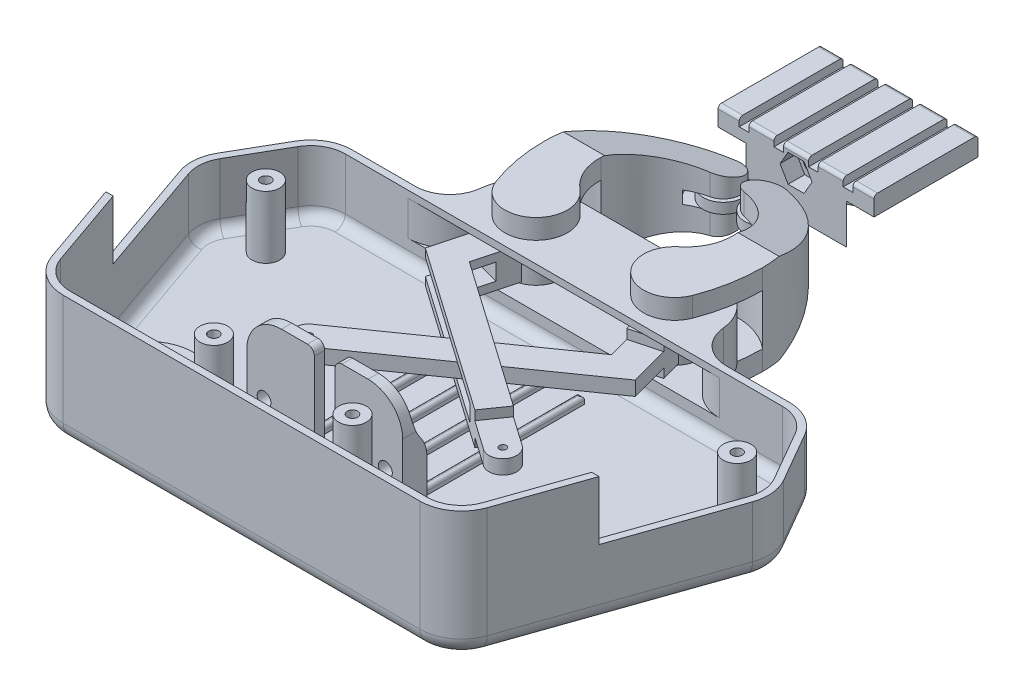
SolidWorks part; units mm, degrees
ref_plane "Front Plane" through (0, 0, 0) normal (0, 0, 1) x (1, 0, 0)
ref_plane "Top Plane" through (0, 0, 0) normal (0, 1, 0) x (1, 0, 0)
ref_plane "Right Plane" through (0, 0, 0) normal (1, 0, 0) x (0, 0, -1)
sketch "Sketch1" plane through (0, 0, 0) normal (0, 1, 0) x (1, 0, 0)
  line L0 (-70, -55) -> (-35, -55)
  line L1 (70, -55) -> (84.4338, -80)
  line L2 (84.4338, -80) -> (60, -150)
  line L3 (60, -150) -> (-60, -150)
  line L4 (-60, -150) -> (-84.4338, -80)
  line L5 (-84.4338, -80) -> (-70, -55)
  line L6 (-35, -55) -> (-35, -35)
  line L7 (-35, -35) -> (35, -35)
  line L8 (35, -35) -> (35, -55)
  line L9 (0, -55) -> (0, -122.8119) construction
  line L10 (35, -55) -> (70, -55)
  point P15 (0, -150)
  dimension "D1" = 25
  dimension "D2" = 140
  dimension "D3" = 70
  dimension "D4" = 120
  dimension "D5" = 70
  dimension "D6" = 55
  dimension "D7" = 120
  dimension "D8" = 20
  dimension "D9" = 70
  dimension "D10" = 35
extrude "Boss-Extrude1" add sketch "Sketch1" along normal blind 2
sketch "Sketch2" plane through (0, 2, 0) normal (0, 1, 0) x (1, 0, 0)
  line L0 (84.4338, -80) -> (70, -55) construction
  line L1 (60, -150) -> (84.4338, -80) construction
  line L2 (-60, -150) -> (60, -150) construction
  line L3 (-84.4338, -80) -> (-60, -150) construction
  line L4 (-70, -55) -> (-84.4338, -80) construction
  line L6 (84.4338, -80) -> (70, -55)
  line L7 (60, -150) -> (84.4338, -80)
  line L8 (-60, -150) -> (60, -150)
  line L9 (-84.4338, -80) -> (-60, -150)
  line L10 (-70, -55) -> (-84.4338, -80)
  line L11 (70, -55) -> (35, -55)
  line L12 (68.8453, -57) -> (33, -57)
  line L13 (-68.8453, -57) -> (-82.2434, -80.2062)
  line L14 (-82.2434, -80.2062) -> (-58.5798, -148)
  line L15 (-58.5798, -148) -> (58.5798, -148)
  line L16 (58.5798, -148) -> (82.2434, -80.2062)
  line L17 (82.2434, -80.2062) -> (68.8453, -57)
  line L18 (-35, -55) -> (-35, -35)
  line L19 (-35, -35) -> (35, -35)
  line L20 (35, -35) -> (35, -55)
  line L21 (-35, -55) -> (-70, -55)
  line L22 (-33, -57) -> (-33, -37)
  line L23 (70, -55) -> (-70, -55) construction
  line L24 (-33, -37) -> (33, -37)
  line L25 (33, -37) -> (33, -57)
  line L26 (-33, -57) -> (-68.8453, -57)
  line L28 (68.8453, -57) -> (-68.8453, -57) construction
  dimension "D1" = 2
  dimension "D2" = 2
  dimension "D3" = 2
  dimension "D4" = 2
extrude "Boss-Extrude2" add sketch "Sketch2" along normal blind 35
sketch "Sketch20" plane through (0, 0, 0) normal (0, -1, 0) x (1, 0, 0)
  line L0 (70, 55) -> (35, 55) construction
  line L1 (-35, 35) -> (35, 35)
  line L2 (-35, 35) -> (-35, 55)
  line L3 (-35, 55) -> (35, 55)
  line L4 (35, 35) -> (35, 55)
  line L5 (35, 55) -> (35, 35) construction
  line L6 (35, 35) -> (-35, 35) construction
  line L7 (-35, 35) -> (-35, 55) construction
extrude "Cut-Extrude7" cut sketch "Sketch20" against normal blind 8
sketch "Sketch21" plane through (0, 8, 0) normal (0, -1, 0) x (1, 0, 0)
  line L1 (-35, 35) -> (35, 35)
  line L2 (-35, 35) -> (-35, 55)
  line L3 (-35, 55) -> (35, 55)
  line L4 (35, 35) -> (35, 55)
extrude "Boss-Extrude12" add sketch "Sketch21" along normal blind 2
sketch "Sketch22" plane through (0, 0, 55) normal (0, 0, 1) x (1, 0, 0)
  line L1 (-33, 2) -> (33, 2)
  line L2 (-33, 2) -> (-33, 8)
  line L3 (-33, 8) -> (33, 8)
  line L4 (33, 2) -> (33, 8)
extrude "Boss-Extrude13" add sketch "Sketch22" along normal blind 2
sketch "Sketch23" plane through (0, 37, 0) normal (0, 1, 0) x (1, 0, 0)
  line L0 (35, -35) -> (-35, -35) construction
  line L1 (-35, -57) -> (35, -57)
  line L2 (-35, -57) -> (-35, -35)
  line L3 (-35, -35) -> (35, -35)
  line L4 (35, -57) -> (35, -35)
  line L5 (-35, -35) -> (-35, -55) construction
  line L6 (35, -55) -> (35, -35) construction
  line L7 (33, -57) -> (-33, -57) construction
extrude "Cut-Extrude8" cut sketch "Sketch23" against normal offset from surface (19 mm away) 12 up to face at (0, 6, 45)
sketch "Sketch24" plane through (0, 18, 0) normal (0, 1, 0) x (1, 0, 0)
  line L1 (-35, -35) -> (35, -35)
  line L2 (-35, -35) -> (-35, -57)
  line L3 (-35, -57) -> (35, -57)
  line L4 (35, -35) -> (35, -57)
  line L5 (-35, -35) -> (35, -35) construction
  line L6 (-35, -55) -> (-35, -35) construction
  line L8 (35, -35) -> (35, -55) construction
  line L9 (-35, -57) -> (-68.8453, -57) construction
extrude "Boss-Extrude16" add sketch "Sketch24" along normal blind 2
sketch "Sketch26" plane through (0, 0, 0) normal (0, -1, 0) x (1, 0, 0)
  line L0 (0, 35) -> (0, 168.1743) construction
  line L1 (-35, 35) -> (35, 35) construction
  circle A0 centre (20, 45) radius 7.5
  circle A1 centre (-20, 45) radius 7.5
  dimension "D1" = 15
  dimension "D2" = 10
  dimension "D3" = 20
extrude "Cut-Extrude9" cut sketch "Sketch26" against normal through all
sketch "Sketch27" plane through (0, 8, 0) normal (0, 1, 0) x (1, 0, 0)
  line L0 (-29.5, -45) -> (-27.5, -45)
  line L1 (-10.5, -45) -> (-12.5, -45)
  line L2 (0, -35) -> (0, -72.4721) construction
  line L3 (35, -35) -> (-35, -35) construction
  line L4 (29.5, -45) -> (27.5, -45)
  line L5 (10.5, -45) -> (12.5, -45)
  arc A0 (-27.5, -45) -> (-12.5, -45) centre (-20, -45) cw
  circle A1 centre (-20, -45) radius 7.5 construction
  arc A2 (-10.5, -45) -> (-29.5, -45) centre (-20, -45) ccw
  arc A3 (27.5, -45) -> (12.5, -45) centre (20, -45) ccw
  arc A4 (10.5, -45) -> (29.5, -45) centre (20, -45) cw
  dimension "D1" = 9.5
extrude "Boss-Extrude18" add sketch "Sketch27" along normal up to surface (10 mm away) up to face at (20, 18, 52.5)
sketch "Sketch25" plane through (0, 20, 0) normal (0, 1, 0) x (1, 0, 0)
  line L0 (35, -57) -> (35, -55) construction
  line L1 (-35, -57) -> (35, -57)
  line L2 (-35, -57) -> (-35, -55)
  line L3 (-35, -55) -> (35, -55)
  line L4 (35, -57) -> (35, -55)
  line L5 (-35, -57) -> (35, -57) construction
  line L6 (-35, -55) -> (-35, -57) construction
  line L7 (-35, -55) -> (-70, -55) construction
extrude "Boss-Extrude17" add sketch "Sketch25" along normal up to surface (17 mm away) up to face at (0, 37, 85.2758)
fillet "Fillet8" radius 10 2 edges at (-33, 13, 37) (33, 13, 37)
fillet "Fillet9" radius 12 2 edges at (35, 13, 35) (-35, 13, 35)
sketch "Sketch32" plane through (0, 6, 0) normal (0, -1, 0) x (1, 0, 0)
  circle A0 centre (-20, 45) radius 7.35
  circle A1 centre (-20, 45) radius 7.5 construction
  dimension "D1" = 14.7
extrude "Boss-Extrude22" add sketch "Sketch32" against normal offset from surface (14.6 mm away) 0.3 from offset 0.3 separate body up to face at (0, 20, 44.8382) offset beyond the face yes
ref_plane "Plane6" through (0, 13, 0) normal (0, -1, 0) x (-1, 0, 0)
sketch "Sketch34" plane through (0, 13, 0) normal (0, -1, 0) x (-1, 0, 0)
  line L0 (0, -55) -> (0, -6.1056) construction
  line L1 (-35, -55) -> (35, -55) construction
  circle A0 centre (6, -5) radius 6
  circle A1 centre (20, -45) radius 7.5 construction
  circle A2 centre (20, -45) radius 7.5 construction
  circle A3 centre (6, -5) radius 2.8
  dimension "D1" = 12
  dimension "D3" = 5.6
  dimension "D2" = 40
extrude "Boss-Extrude23" add sketch "Sketch34" along normal mid plane 3 separate body
sketch "Sketch36" plane through (0, 13, 0) normal (0, -1, 0) x (-1, 0, 0)
  circle A0 centre (6, -5) radius 2.5
  dimension "D1" = 5
extrude "Boss-Extrude24" add sketch "Sketch36" along normal mid plane 3.6 separate body
sketch "Sketch37" plane through (0, 11.2, 0) normal (0, -1, 0) x (1, 0, 0)
  line L0 (-1.0405, 27.7489) -> (-20, 45) construction
  line L1 (-6, 5) -> (-1.0405, 27.7489) construction
  line L2 (0.4875, 31.2396) -> (-20, 45) construction
  line L3 (0.4875, 31.2396) -> (-6, 5) construction
  arc A0 (-4.935, 9.8853) -> (-7.2001, 0.1462) centre (-6, 5) cw
  circle A1 centre (-20, 45) radius 7.35 construction
  arc A2 (-14.5636, 40.0535) -> (-26.1015, 49.0981) centre (-20, 45) ccw construction
  arc A3 (-4.935, 9.8853) -> (-14.5636, 40.0535) centre (-1.0405, 27.7489) cw construction
  arc A4 (-26.1015, 49.0981) -> (-7.2001, 0.1462) centre (0.4875, 31.2396) ccw construction
  arc A5 (-31.5421, 31.1877) -> (-19.3089, 27.0133) centre (-20, 45) ccw
  arc A6 (-31.5421, 31.1877) -> (-7.2001, 0.1462) centre (0.4875, 31.2396) ccw
  arc A7 (-19.3089, 27.0133) -> (-4.935, 9.8853) centre (-1.0405, 27.7489) ccw
  dimension "D1" = 5
  dimension "D4" = 18
  dimension "D2" = 60
  dimension "D3" = 70
extrude "Boss-Extrude25" add sketch "Sketch37" along normal up to surface (11.2 mm away) up to face at (0, 0, 95)
sketch "Sketch39" plane through (0, 5.7, 0) normal (0, -1, 0) x (1, 0, 0)
  arc A0 (-14.3353, 38.0064) -> (-28.4038, 48.2211) centre (-20, 45) ccw
  arc A1 (-31.5421, 31.1877) -> (-19.3089, 27.0133) centre (-20, 45) ccw construction
  arc A2 (-31.5421, 31.1877) -> (-19.3089, 27.0133) centre (-20, 45) ccw
  arc A3 (-31.5421, 31.1877) -> (-28.4038, 48.2211) centre (15.8356, 31.2644) cw
  arc A4 (-31.5421, 31.1877) -> (-7.2001, 0.1462) centre (0.4875, 31.2396) ccw construction
  arc A5 (-19.3089, 27.0133) -> (-14.3353, 38.0064) centre (-5.8694, 27.5545) cw
  arc A6 (-19.3089, 27.0133) -> (-4.935, 9.8853) centre (-1.0405, 27.7489) ccw construction
  dimension "D1" = 18
extrude "Boss-Extrude26" add sketch "Sketch39" along direction (0, -1, 0) on the side of the normal up to surface (5.7 mm away) up to face at (-16.6764, 0, 14.8256)
sketch "Sketch40" plane through (0, 20.3, 0) normal (0, 1, 0) x (1, 0, 0)
  arc A1 (-28.4038, -48.2211) -> (-14.3353, -38.0064) centre (-20, -45) ccw construction
  arc A2 (-19.3089, -27.0133) -> (-14.3353, -38.0064) centre (-5.8694, -27.5545) ccw construction
  arc A3 (-19.3089, -27.0133) -> (-31.5421, -31.1877) centre (-20, -45) ccw construction
  arc A4 (-31.5421, -31.1877) -> (-28.4038, -48.2211) centre (15.8356, -31.2644) ccw construction
  arc A5 (-28.4038, -48.2211) -> (-14.3353, -38.0064) centre (-20, -45) ccw
  arc A6 (-19.3089, -27.0133) -> (-14.3353, -38.0064) centre (-5.8694, -27.5545) ccw
  arc A7 (-19.3089, -27.0133) -> (-31.5421, -31.1877) centre (-20, -45) ccw
  arc A8 (-31.5421, -31.1877) -> (-28.4038, -48.2211) centre (15.8356, -31.2644) ccw
extrude "Boss-Extrude27" add sketch "Sketch40" along normal blind 5.7
sketch "Sketch41" plane through (0, 14.8, 0) normal (0, 1, 0) x (1, 0, 0)
  arc A0 (-4.935, -9.8853) -> (-7.2001, -0.1462) centre (-6, -5) ccw construction
  arc A1 (-19.3089, -27.0133) -> (-31.5421, -31.1877) centre (-20, -45) ccw construction
  arc A2 (-4.935, -9.8853) -> (-19.3089, -27.0133) centre (-1.0405, -27.7489) ccw construction
  arc A3 (-7.2001, -0.1462) -> (-31.5421, -31.1877) centre (0.4875, -31.2396) ccw construction
  arc A4 (-4.935, -9.8853) -> (-7.2001, -0.1462) centre (-6, -5) ccw
  arc A5 (-19.3089, -27.0133) -> (-31.5421, -31.1877) centre (-20, -45) ccw
  arc A6 (-4.935, -9.8853) -> (-19.3089, -27.0133) centre (-1.0405, -27.7489) ccw
  arc A7 (-7.2001, -0.1462) -> (-31.5421, -31.1877) centre (0.4875, -31.2396) ccw
extrude "Boss-Extrude28" add sketch "Sketch41" along normal up to surface (11.2 mm away) up to face at (-22.3518, 26, 38.2988)
sketch "Sketch43" plane through (0, 11.2, 0) normal (0, 1, 0) x (1, 0, 0)
  arc A1 (-4.935, -9.8853) -> (-19.3089, -27.0133) centre (-1.0405, -27.7489) ccw construction
  arc A3 (-19.3089, -27.0133) -> (-31.5421, -31.1877) centre (-20, -45) ccw construction
  arc A5 (-10.5871, -12.156) -> (-19.3089, -27.0133) centre (-1.0405, -27.7489) ccw
  arc A6 (-7.2001, -0.1462) -> (-31.5421, -31.1877) centre (0.4875, -31.2396) ccw construction
  arc A7 (-19.3089, -27.0133) -> (-31.5421, -31.1877) centre (-20, -45) ccw
  arc A8 (-14.2045, -2.7783) -> (-10.5871, -12.156) centre (-6, -5) ccw
  arc A9 (-14.2045, -2.7783) -> (-31.5421, -31.1877) centre (0.4875, -31.2396) ccw
  arc A13 (-4.935, -9.8853) -> (-7.2001, -0.1462) centre (-6, -5) ccw construction
  dimension "D1" = 17
extrude "Boss-Extrude29" add sketch "Sketch43" along normal up to surface (3.6 mm away) up to face at (-6, 14.8, 2.5)
sketch "Sketch44" plane through (0, 0, 0) normal (1, 0, 0) x (0, 0, -1)
  line L0 (0, 17.8) -> (-26.0133, 26)
  line L1 (-26.0133, 26) -> (0, 26)
  line L4 (0, 14.8) -> (0, 26) construction
  line L5 (-9.8853, 26) -> (-27.0133, 26) construction
  line L6 (0, 17.8) -> (0, 26)
  line L7 (-15.422, 13) -> (22.0298, 13) construction
  line L8 (-94.4278, 13) -> (94.4278, 13) construction
  line L9 (0, 8.2) -> (-26.0133, 0)
  line L10 (-26.0133, 0) -> (0, 0)
  line L11 (0, 8.2) -> (0, 0)
  dimension "D1" = 1
  dimension "D2" = 3
extrude "Cut-Extrude10" cut sketch "Sketch44" against normal up to surface (31.1129 mm away) up to face at (-19.4224, 13, 12.2098)
ref_plane "Plane2" through (0, 0, 0) normal (1, 0, 0) x (0, 0, -1)
ref_plane "Plane3" through (0, 0, 126) normal (0, 0, -1) x (-1, 0, 0)
sketch "Sketch45" plane through (0, 13, 0) normal (0, -1, 0) x (-1, 0, 0)
  circle A0 centre (6, -5) radius 6 construction
  circle A1 centre (6, -5) radius 6
  circle A2 centre (6, -5) radius 5.75
  dimension "D1" = 11.5
extrude "Cut-Extrude11" cut sketch "Sketch45" along normal up to surface (1.5 mm away) from surface up to face at (-6, 11.5, -1) starting at face at (-6, 14.5, -1)
mirror "Mirror8" about plane through (0, 0, 0) normal (1, 0, 0) of bodies 137 140
sketch "Sketch8" plane through (0, 0, 126) normal (0, 0, -1) x (-1, 0, 0)
  line L0 (-68.8453, 2) -> (68.8453, 2) construction
  line L1 (-68.8453, 2) -> (68.8453, 2) construction
  line L2 (60, 0) -> (-60, 0) construction
  line L3 (22.5, 2) -> (-22.5, 2)
  line L4 (22.5, 2) -> (22.5, 36)
  line L5 (22.5, 36) -> (-22.5, 36)
  line L6 (-22.5, 2) -> (-22.5, 36)
  line L7 (60, 0) -> (-60, 0) construction
  line L8 (0, 14.8493) -> (0, -14.8493) construction
  dimension "D1" = 34
  dimension "D2" = 45
  dimension "D3" = 22.5
extrude "Boss-Extrude5" add sketch "Sketch8" along normal blind 3
sketch "Sketch9" plane through (0, 2, 0) normal (0, 1, 0) x (1, 0, 0)
  line L1 (-22.5, -123) -> (-19.5, -123)
  line L2 (-22.5, -123) -> (-22.5, -119)
  line L3 (-22.5, -119) -> (-19.5, -119)
  line L4 (-19.5, -123) -> (-19.5, -119)
  line L5 (22.5, -123) -> (19.5, -123)
  line L6 (22.5, -123) -> (22.5, -119)
  line L7 (22.5, -119) -> (19.5, -119)
  line L8 (19.5, -123) -> (19.5, -119)
  dimension "D1" = 3
  dimension "D2" = 4
extrude "Boss-Extrude6" add sketch "Sketch9" along normal blind 20
fillet "Fillet1" radius 10 2 edges at (-21, 22, 123) (21, 22, 123)
fillet "Fillet2" radius 10 2 edges at (-21, 22, 119) (21, 22, 119)
sketch "Sketch11" plane through (0, 2, 0) normal (0, 1, 0) x (1, 0, 0)
  line L0 (-58.5798, -148) -> (58.5798, -148) construction
  circle A0 centre (-43.5798, -133) radius 12.5
  dimension "D1" = 25
  dimension "D2" = 15
  dimension "D3" = 15
extrude "Boss-Extrude9" add sketch "Sketch11" along normal blind 10
ref_plane "Plane4" through (0, 7, 0) normal (0, 1, 0) x (1, 0, 0)
sketch "Sketch13" plane through (0, 7, 0) normal (0, 1, 0) x (1, 0, 0)
  line L0 (-53.0211, -136.2955) -> (-58.294, -121.1894)
  line L1 (-82.2434, -80.2062) -> (-58.5798, -148) construction
  line L2 (-34.1384, -129.7045) -> (-39.4113, -114.5983)
  line L3 (-58.294, -121.1894) -> (-39.4113, -114.5983)
  arc A0 (-53.0211, -136.2955) -> (-34.1384, -129.7045) centre (-43.5798, -133) ccw
  dimension "D1" = 20
  dimension "D2" = 16
extrude "Cut-Extrude3" cut sketch "Sketch13" along normal blind 5 from offset 3 offset against normal yes
sketch "Sketch14" plane through (0, 12, 0) normal (0, 1, 0) x (1, 0, 0)
  circle A0 centre (-43.5798, -133) radius 2.5
  circle A1 centre (-43.5798, -133) radius 12.5 construction
  dimension "D1" = 5
extrude "Cut-Extrude4" cut sketch "Sketch14" against normal up to surface (8 mm away) up to face at (-44.4037, 4, 130.6397)
sketch "Sketch15" plane through (0, 0, 126) normal (0, 0, 1) x (1, 0, 0)
  line L1 (22.5, 2) -> (-22.5, 2) construction
  line L2 (22.5, 2) -> (-22.5, 2) construction
  line L3 (0, -14.8493) -> (0, 14.8493) construction
  circle A0 centre (17.5, 16) radius 2
  circle A1 centre (-17.5, 16) radius 2
  circle A3 centre (0, 8) radius 4.65
  dimension "D1" = 8
  dimension "D2" = 4
  dimension "D3" = 4
  dimension "D6" = 9.3
  dimension "D4" = 35
  dimension "D5" = 17.5
  dimension "D7" = 6
extrude "Cut-Extrude5" cut sketch "Sketch15" against normal up to surface (3 mm away) up to face at (0, 24.5, 123)
fillet "Fillet3" radius 10 8 edges at (-35, 13, 55) (35, 13, 55) (58.5798, 19.5, 148) (-58.5798, 19.5, 148) (82.2434, 19.5, 80.2062) (68.8453, 19.5, 57) (-82.2434, 19.5, 80.2062) (-68.8453, 19.5, 57)
fillet "Fillet4" radius 12 8 edges at (-60, 18.5, 150) (-84.4338, 18.5, 80) (-70, 18.5, 55) (-33, 13, 57) (33, 13, 57) (70, 18.5, 55) (60, 18.5, 150) (84.4338, 18.5, 80)
fillet "Fillet5" radius 10 2 edges at (22.5, 36, 124.5) (-22.5, 36, 124.5)
fillet "Fillet6" radius 3 12 edges at (-70.8266, 2, 112.9143) (-81.2478, 2, 80.3) (-75.842, 2, 69.1187) (-68.0718, 2, 58.3397) (0, 2, 57) (68.0718, 2, 58.3397) (75.842, 2, 69.1187) (81.2478, 2, 80.3) (70.8266, 2, 112.9143) (0, 2, 148) (-57.2685, 2, 146.1534) (57.2685, 2, 146.1534)
fillet "Fillet7" radius 5 12 edges at (69.0718, 0, 56.6077) (77.5741, 0, 68.1187) (83.2389, 0, 80.1125) (72.7148, 0, 113.5734) (58.4264, 0, 147.7841) (0, 0, 150) (-58.4264, 0, 147.7841) (-72.7148, 0, 113.5734) (-83.2389, 0, 80.1125) (-77.5741, 0, 68.1187) (-69.0718, 0, 56.6077) (0, 0, 55)
sketch "Sketch16" plane through (0, 0, 0) normal (1, 0, 0) x (0, 0, -1)
  line L0 (-83.5443, 0) -> (-140.3069, 0) construction
  line L1 (-118, 40) -> (-28, 40)
  line L2 (-118, 40) -> (-118, 20)
  line L3 (-118, 20) -> (-28, 20)
  line L4 (-28, 40) -> (-28, 20)
  line L5 (-150, 5) -> (-150, 37) construction
  dimension "D1" = 20
  dimension "D2" = 32
  dimension "D3" = 20
  dimension "D4" = 90
extrude "Cut-Extrude6" cut sketch "Sketch16" against normal through all both and the other way through all
sketch "Sketch17" plane through (0, 2, 0) normal (0, 1, 0) x (1, 0, 0)
  line L0 (0, -14.8493) -> (0, 14.8493) construction
  line L4 (-63.0718, -55) -> (-44.9089, -55) construction
  circle A2 centre (-68, -75) radius 4
  circle A4 centre (-68, -75) radius 1.5
  circle A10 centre (68, -75) radius 1.5
  circle A11 centre (68, -75) radius 4
  dimension "D7" = 8
  dimension "D9" = 3
  dimension "D4" = 20
  dimension "D5" = 68
extrude "Boss-Extrude10" add sketch "Sketch17" along normal up to surface (18 mm away) up to face at (0, 20, 71.1525)
sketch "Sketch19" plane through (0, 2, 0) normal (0, 1, 0) x (1, 0, 0)
  line L0 (0, -14.8493) -> (0, 14.8493) construction
  line L1 (-51.4786, -150) -> (51.4786, -150) construction
  circle A0 centre (-20, -138) radius 4
  circle A1 centre (-20, -138) radius 1.5
  circle A2 centre (20, -138) radius 1.5
  circle A3 centre (20, -138) radius 4
  dimension "D1" = 3
  dimension "D2" = 8
  dimension "D3" = 20
  dimension "D4" = 12
extrude "Boss-Extrude11" add sketch "Sketch19" along normal up to surface (35 mm away) up to face at (0, 37, 136.7604)
sketch "Sketch46" plane through (0, 0, 126) normal (0, 0, 1) x (1, 0, 0)
  line L0 (-3, 8) -> (-3, 36)
  line L1 (-3, 36) -> (3, 36)
  line L3 (-3, 8) -> (3, 8)
  line L5 (-12.5, 36) -> (12.5, 36) construction
  line L7 (3, 36) -> (3, 8)
  circle A0 centre (0, 8) radius 4.65 construction
  circle A1 centre (0, 8) radius 4.65 construction
  dimension "D1" = 6
extrude "Cut-Extrude12" cut sketch "Sketch46" against normal up to surface (3 mm away) up to face at (-4.65, 8, 123)
fillet "Fillet10" radius 2 2 edges at (-3, 36, 124.5) (3, 36, 124.5)
mirror "Mirror9" about plane through (0, 0, 0) normal (1, 0, 0) of "Cut-Extrude4", "Cut-Extrude3", "Boss-Extrude9"
sketch "Sketch49" plane through (0, 13, 0) normal (0, -1, 0) x (-1, 0, 0)
  line L0 (20, -45) -> (6, -5) construction
  line L1 (27.0996, -43.0977) -> (32.923, -64.831) construction
  line L2 (30.3078, -66.6622) -> (-25.7197, -105.8931)
  line L3 (12.9004, -46.9023) -> (17.9052, -65.5804) construction
  line L4 (17.9052, -65.5804) -> (-30.3083, -99.3398)
  line L5 (63.0718, -57) -> (-63.0718, -57) construction
  line L6 (30.3078, -66.6622) -> (25.7352, -49.5968)
  line L7 (20.5204, -63.7492) -> (17.3316, -51.8485)
  line L8 (17.9052, -65.5804) -> (20.5204, -63.7492)
  line L9 (30.3078, -66.6622) -> (32.923, -64.831) construction
  circle A0 centre (20, -45) radius 7.35 construction
  arc A1 (17.3316, -51.8485) -> (25.7352, -49.5968) centre (20, -45) ccw
  circle A2 centre (20, -45) radius 75 construction
  arc A3 (7.2001, -0.1462) -> (4.935, -9.8853) centre (6, -5) ccw construction
  arc A4 (7.2001, -0.1462) -> (4.935, -9.8853) centre (6, -5) ccw construction
  arc A5 (-30.3083, -99.3398) -> (-25.7197, -105.8931) centre (-28.014, -102.6165) ccw
  point P15 (26.4546, -40.6906)
  point P19 (0, 0)
  point P20 (27.0996, -43.0977)
  dimension "D1" = 150
  dimension "D2" = 110
  dimension "D3" = 4
  dimension "D4" = 22.5
  dimension "D5" = 35
  dimension "D6" = 3
  dimension "D7" = 3
extrude "Boss-Extrude30" add sketch "Sketch49" along normal offset from surface 0.3 and the other way offset from surface 0.3 separate body up to face at (0, 8, 45.5486) other way up to face at (0, 18, 45.5486)
sketch "Sketch50" plane through (-41.2919, 0, 58.971) normal (-0.5736, 0, 0.8192) x (0.8192, 0, 0.5736)
  line L0 (13.4091, 8.3) -> (13.4091, 17.7) construction
  line L1 (13.4091, 15.4) -> (65.8061, 15.4)
  line L2 (13.4091, 15.4) -> (13.4091, 10.6)
  line L3 (13.4091, 10.6) -> (65.8061, 10.6)
  line L4 (65.8061, 15.4) -> (65.8061, 10.6)
  line L5 (85.8061, 8.3) -> (85.8061, 17.7) construction
  line L6 (13.4091, 15.4) -> (13.4091, 17.7) construction
  line L7 (81.8061, 17.7) -> (13.4091, 17.7) construction
  line L8 (13.4091, 10.6) -> (13.4091, 8.3) construction
  line L9 (13.4091, 8.3) -> (81.8061, 8.3) construction
  dimension "D1" = 4.8
  dimension "D2" = 0
  dimension "D3" = 20
extrude "Cut-Extrude13" cut sketch "Sketch50" against normal up to surface (8 mm away) up to face at (4.894, 13, 81.5445)
sketch "Sketch51" plane through (0, 13, 0) normal (0, -1, 0) x (-1, 0, 0)
  line L0 (30.3078, -66.6622) -> (25.7352, -49.5968) construction
  line L1 (17.3316, -51.8485) -> (20.5204, -63.7492) construction
  line L3 (-25.7197, -105.8931) -> (30.3078, -66.6622) construction
  line L6 (20.5204, -63.7492) -> (-30.3083, -99.3398) construction
  line L22 (17.3316, -51.8485) -> (20.5204, -63.7492) construction
  line L23 (20.5204, -63.7492) -> (-30.3083, -99.3398) construction
  line L24 (-25.7197, -105.8931) -> (30.3078, -66.6622) construction
  line L25 (30.3078, -66.6622) -> (25.7352, -49.5968) construction
  line L26 (0, 14.8493) -> (0, -14.8493) construction
  line L27 (-20.5204, -63.7492) -> (30.3083, -99.3398)
  line L28 (-17.3316, -51.8485) -> (-20.5204, -63.7492)
  line L29 (-30.3078, -66.6622) -> (-25.7352, -49.5968)
  line L30 (25.7197, -105.8931) -> (-30.3078, -66.6622)
  arc A0 (17.3316, -51.8485) -> (25.7352, -49.5968) centre (20, -45) ccw construction
  arc A6 (-30.3083, -99.3398) -> (-25.7197, -105.8931) centre (-28.014, -102.6165) ccw construction
  arc A10 (-30.3083, -99.3398) -> (-25.7197, -105.8931) centre (-28.014, -102.6165) ccw construction
  arc A11 (17.3316, -51.8485) -> (25.7352, -49.5968) centre (20, -45) ccw construction
  arc A12 (30.3083, -99.3398) -> (25.7197, -105.8931) centre (28.014, -102.6165) cw
  arc A13 (-17.3316, -51.8485) -> (-25.7352, -49.5968) centre (-20, -45) cw
extrude "Boss-Extrude32" add sketch "Sketch51" along normal offset from surface 0.3 and the other way offset from surface 0.4 up to face at (-9.3465, 10.6, 75.4798) other way up to face at (-9.3465, 15.4, 75.4798)
sketch "Sketch52" plane through (0, 13, 0) normal (0, -1, 0) x (-1, 0, 0)
  line L2 (-25.7352, -49.5968) -> (-30.3078, -66.6622) construction
  line L3 (-20.5204, -63.7492) -> (-17.3316, -51.8485) construction
  line L6 (-25.7352, -49.5968) -> (-27.3076, -55.4652)
  line L7 (-18.9041, -57.717) -> (-17.3316, -51.8485)
  line L9 (-18.9041, -57.717) -> (-27.3076, -55.4652)
  line L10 (63.0718, -57) -> (-63.0718, -57) construction
  arc A0 (-25.7352, -49.5968) -> (-17.3316, -51.8485) centre (-20, -45) ccw construction
  arc A1 (-25.7352, -49.5968) -> (-17.3316, -51.8485) centre (-20, -45) ccw
  circle A2 centre (-20, -45) radius 12 construction
  point P2 (-27.4936, -56.1593)
extrude "Boss-Extrude33" add sketch "Sketch52" along normal up to surface (4.7 mm away) from surface up to face at (-5.8265, 8.3, 73.4601) starting at face at (-5.8265, 17.7, 73.4601)
sketch "Sketch53" plane through (0, 17.7, 0) normal (0, 1, 0) x (1, 0, 0)
  line L0 (-20.5204, -63.7492) -> (30.3083, -99.3398) construction
  line L1 (25.7197, -105.8931) -> (-30.3078, -66.6622) construction
  line L2 (21.8792, -93.4377) -> (30.3083, -99.3398)
  line L3 (25.7197, -105.8931) -> (17.2906, -99.9909)
  line L4 (17.2906, -99.9909) -> (21.8792, -93.4377)
  arc A0 (25.7197, -105.8931) -> (30.3083, -99.3398) centre (28.014, -102.6165) ccw construction
  arc A1 (25.7197, -105.8931) -> (30.3083, -99.3398) centre (28.014, -102.6165) ccw
  point P5 (31.2906, -104.9108)
  dimension "D1" = 14
extrude "Cut-Extrude14" cut sketch "Sketch53" against normal up to surface (2.7 mm away) up to face at (6.2892, 15, 75.1868)
sketch "Sketch54" plane through (0, 8.3, 0) normal (0, -1, 0) x (1, 0, 0)
  line L0 (25.7197, 105.8931) -> (17.2906, 99.9909) construction
  line L1 (21.8792, 93.4377) -> (30.3083, 99.3398) construction
  line L2 (17.2906, 99.9909) -> (21.8792, 93.4377) construction
  line L3 (25.7197, 105.8931) -> (17.2906, 99.9909)
  line L4 (21.8792, 93.4377) -> (30.3083, 99.3398)
  line L5 (17.2906, 99.9909) -> (21.8792, 93.4377)
  arc A0 (30.3083, 99.3398) -> (25.7197, 105.8931) centre (28.014, 102.6165) ccw construction
  arc A1 (30.3083, 99.3398) -> (25.7197, 105.8931) centre (28.014, 102.6165) ccw
extrude "Cut-Extrude15" cut sketch "Sketch54" against normal up to surface (2.6 mm away) up to face at (6.2892, 10.9, 75.1868)
sketch "Sketch55" plane through (0, 15, 0) normal (0, 1, 0) x (1, 0, 0)
  arc A0 (-30.3083, -99.3398) -> (-25.7197, -105.8931) centre (-28.014, -102.6165) ccw construction
  arc A1 (25.7197, -105.8931) -> (30.3083, -99.3398) centre (28.014, -102.6165) ccw construction
  arc A2 (-30.3083, -99.3398) -> (-25.7197, -105.8931) centre (-28.014, -102.6165) ccw construction
  arc A3 (25.7197, -105.8931) -> (30.3083, -99.3398) centre (28.014, -102.6165) ccw construction
  circle A4 centre (-28.014, -102.6165) radius 1
  circle A5 centre (28.014, -102.6165) radius 1
  dimension "D1" = 2
  dimension "D2" = 2
extrude "Cut-Extrude16" cut sketch "Sketch55" against normal up to surface (4.1 mm away) up to face at (6.2892, 10.9, 75.1868)
sketch "Sketch56" plane through (0, 2, 0) normal (0, 1, 0) x (1, 0, 0)
  line L0 (0, -14.8493) -> (0, 14.8493) construction
  line L1 (-16, -119) -> (-14, -119)
  line L2 (-16, -119) -> (-16, -67)
  line L3 (-16, -67) -> (-14, -67)
  line L4 (-14, -119) -> (-14, -67)
  line L5 (-6, -119) -> (-4, -119)
  line L6 (-6, -119) -> (-6, -67)
  line L7 (-6, -67) -> (-4, -67)
  line L8 (-4, -119) -> (-4, -67)
  line L9 (-63.0718, -57) -> (63.0718, -57) construction
  point P10 (-7.2699, -121.6995)
  point P11 (0, 0)
  point P12 (0, 0)
  point P16 (0, 0)
  dimension "D1" = 4
  dimension "D2" = 8
  dimension "D3" = 10
  dimension "D4" = 2
extrude "Boss-Extrude34" add sketch "Sketch56" along normal blind 2
fillet "Fillet11" radius 1 8 edges at (-15, 4, 119) (-5, 4, 119) (-5, 4, 67) (-15, 4, 67) (-4, 4, 93) (-6, 4, 93) (-14, 4, 93) (-16, 4, 93)
mirror "Mirror11" about plane through (0, 0, 0) normal (1, 0, 0) of "Fillet11", "Boss-Extrude34"
sketch "Sketch58" plane through (0, 2, 0) normal (0, 1, 0) x (1, 0, 0)
  line L0 (-22.5, -119) -> (-22.5, -126) construction
  line L1 (-22.5, 40) -> (22.5, 40)
  line L2 (-22.5, 40) -> (-22.5, 10)
  line L3 (-22.5, 10) -> (22.5, 10)
  line L4 (22.5, 40) -> (22.5, 10)
  line L5 (22.5, -119) -> (22.5, -126) construction
  line L6 (23, -35) -> (-23, -35) construction
  dimension "D1" = 30
  dimension "D2" = 45
extrude "Boss-Extrude35" add sketch "Sketch58" along normal offset from surface (17 mm away) 1 separate body up to face at (0, 20, 71.1525)
sketch "Sketch60" plane through (0, 19, 0) normal (0, 1, 0) x (1, 0, 0)
  line L0 (-14, -119) -> (-14, -67) construction
  line L1 (-4, -119) -> (-4, -67) construction
  line L2 (6, -67) -> (6, -119) construction
  line L3 (16, -67) -> (16, -119) construction
  line L4 (14, -119) -> (14, -67) construction
  line L5 (4, -119) -> (4, -67) construction
  line L6 (-6, -67) -> (-6, -119) construction
  line L7 (-16, -67) -> (-16, -119) construction
  line L8 (-14, -119) -> (-14, -67) construction
  line L9 (-4, -119) -> (-4, -67) construction
  line L10 (6, -67) -> (6, -119) construction
  line L11 (16, -46.9969) -> (16, -119) construction
  line L12 (14, -119) -> (14, -67) construction
  line L13 (4, -119) -> (4, -67) construction
  line L14 (-6, -67) -> (-6, -119) construction
  line L15 (-16, -67) -> (-16, -119) construction
  line L16 (16, 40) -> (16, 10) construction
  line L17 (22.5, 40) -> (-22.5, 40) construction
  line L18 (14, 10) -> (14, 40) construction
  line L19 (6, 10) -> (6, 40) construction
  line L20 (4, 10) -> (4, 40) construction
  line L21 (-4, 10) -> (-4, 40) construction
  line L22 (-6, 10) -> (-6, 40) construction
  line L23 (-14, 10) -> (-14, 40) construction
  line L24 (-16, 10) -> (-16, 40) construction
  line L27 (-22.5, 10) -> (22.5, 10) construction
  line L28 (-16, 40) -> (-14, 40) construction
  line L29 (-6, 40) -> (-4, 40) construction
  line L30 (4, 40) -> (6, 40) construction
  line L31 (14, 40) -> (16, 40) construction
  line L32 (16, 10) -> (14, 10) construction
  line L33 (6, 10) -> (4, 10) construction
  line L34 (-4, 10) -> (-6, 10) construction
  line L35 (-14, 10) -> (-16, 10) construction
  line L36 (16.4, 40.4) -> (16.4, 9.6)
  line L37 (16.4, 9.6) -> (13.6, 9.6)
  line L38 (13.6, 9.6) -> (13.6, 40.4)
  line L39 (13.6, 40.4) -> (16.4, 40.4)
  line L40 (6.4, 9.6) -> (6.4, 40.4)
  line L41 (3.6, 40.4) -> (6.4, 40.4)
  line L42 (3.6, 9.6) -> (3.6, 40.4)
  line L43 (6.4, 9.6) -> (3.6, 9.6)
  line L44 (-3.6, 9.6) -> (-3.6, 40.4)
  line L45 (-6.4, 40.4) -> (-3.6, 40.4)
  line L46 (-6.4, 9.6) -> (-6.4, 40.4)
  line L47 (-3.6, 9.6) -> (-6.4, 9.6)
  line L48 (-13.6, 9.6) -> (-13.6, 40.4)
  line L49 (-16.4, 40.4) -> (-13.6, 40.4)
  line L50 (-16.4, 9.6) -> (-16.4, 40.4)
  line L51 (-13.6, 9.6) -> (-16.4, 9.6)
  dimension "D1" = 0.4
extrude "Cut-Extrude17" cut sketch "Sketch60" against normal blind 2.4
fillet "Fillet12" radius 1 10 edges at (-19.45, 19, -10) (-10, 19, -10) (0, 19, -10) (10, 19, -10) (19.45, 19, -10) (19.45, 19, -40) (10, 19, -40) (0, 19, -40) (-10, 19, -40) (-19.45, 19, -40)
sketch "Sketch61" plane through (0, 2, 0) normal (0, -1, 0) x (1, 0, 0)
  line L7 (-22.5, -10) -> (-22.5, -40)
  line L8 (-22.5, -40) -> (22.5, -40)
  line L9 (22.5, -40) -> (22.5, -10)
  line L10 (22.5, -10) -> (14.5, -10)
  line L11 (-22.5, -10) -> (22.5, -10) construction
  line L12 (14.5, -10) -> (6, -18)
  line L13 (6, -18) -> (-6, -18)
  line L15 (-6, -18) -> (-14.5, -10)
  line L16 (-14.5, -10) -> (-22.5, -10)
  dimension "D1" = 8
  dimension "D2" = 8
  dimension "D3" = 8
  dimension "D4" = 12
extrude "Cut-Extrude18" cut sketch "Sketch61" against normal offset from surface (11.5 mm away) 5.5 contours L13 L15 L16 L7 L8 L9 L10 L12 up to face at (-19.45, 19, -25)
sketch "Sketch62" plane through (0, 13.5, 0) normal (0, -1, 0) x (1, 0, 0)
  line L0 (6, -18) -> (-6, -18) construction
  line L1 (0, -18) -> (0, -71.4655) construction
  line L5 (-22.5, -40) -> (22.5, -40) construction
  circle A2 centre (0, -30) radius 10
  point P1 (0, 0)
  dimension "D1" = 20
extrude "Boss-Extrude38" add sketch "Sketch62" along normal up to surface (11.5 mm away) up to face at (0, 2, -14)
sketch "Sketch63" plane through (0, 0, -10) normal (0, 0, 1) x (1, 0, 0)
  line L0 (0, -14.8493) -> (0, 14.8493) construction
  line L1 (-3.6, 19) -> (3.6, 19) construction
  circle A0 centre (0, 13.3) radius 2.9
  point P6 (0, 0)
  dimension "D1" = 5.8
  dimension "D2" = 5.7
extrude "Cut-Extrude19" cut sketch "Sketch63" against normal up to surface (30 mm away) up to face at (0, 16.8238, -40)
sketch "Sketch66" plane through (0, 0, -10) normal (0, 0, 1) x (1, 0, 0)
  line L0 (-3.6, 19) -> (3.6, 19) construction
  line L1 (2.3094, 9.3) -> (4.6188, 13.3)
  line L2 (4.6188, 13.3) -> (2.3094, 17.3)
  line L3 (2.3094, 17.3) -> (-2.3094, 17.3)
  line L4 (-2.3094, 17.3) -> (-4.6188, 13.3)
  line L5 (-4.6188, 13.3) -> (-2.3094, 9.3)
  line L6 (-2.3094, 9.3) -> (2.3094, 9.3)
  circle A0 centre (0, 13.3) radius 4 construction
  point P1 (2.517, 17.1727)
  dimension "D1" = 8
extrude "Cut-Extrude20" cut sketch "Sketch66" against normal blind 4.8
sketch "Sketch67" plane through (-11.612, 0, -3.1114) normal (-0.9659, 0, -0.2588) x (-0.2588, 0, 0.9659)
  line L1 (72.235, 15.4) -> (60.645, 15.4)
  line L2 (72.235, 15.4) -> (72.235, 10.6)
  line L3 (72.235, 10.6) -> (60.645, 10.6)
  line L4 (60.645, 15.4) -> (60.645, 10.6)
  point P5 (0, 0)
  dimension "D1" = 11.59
extrude "Cut-Extrude21" cut sketch "Sketch67" against normal up to surface (8.7 mm away) up to face at (-19.4575, 13, 59.7823)
sketch "Sketch68" plane through (0, 2, 0) normal (0, 1, 0) x (1, 0, 0)
  line L2 (-7.5, -126) -> (-7.5, -147)
  line L3 (-7.5, -147) -> (7.5, -147)
  line L4 (7.5, -126) -> (7.5, -147)
  line L6 (-7.5, -126) -> (7.5, -126)
  line L7 (22.5, -126) -> (-22.5, -126) construction
  line L8 (0, -14.8493) -> (0, 14.8493) construction
  dimension "D1" = 21
  dimension "D2" = 15
  dimension "D3" = 7.5
extrude "Cut-Extrude22" cut sketch "Sketch68" along normal blind 5 from offset 1 offset against normal yes
